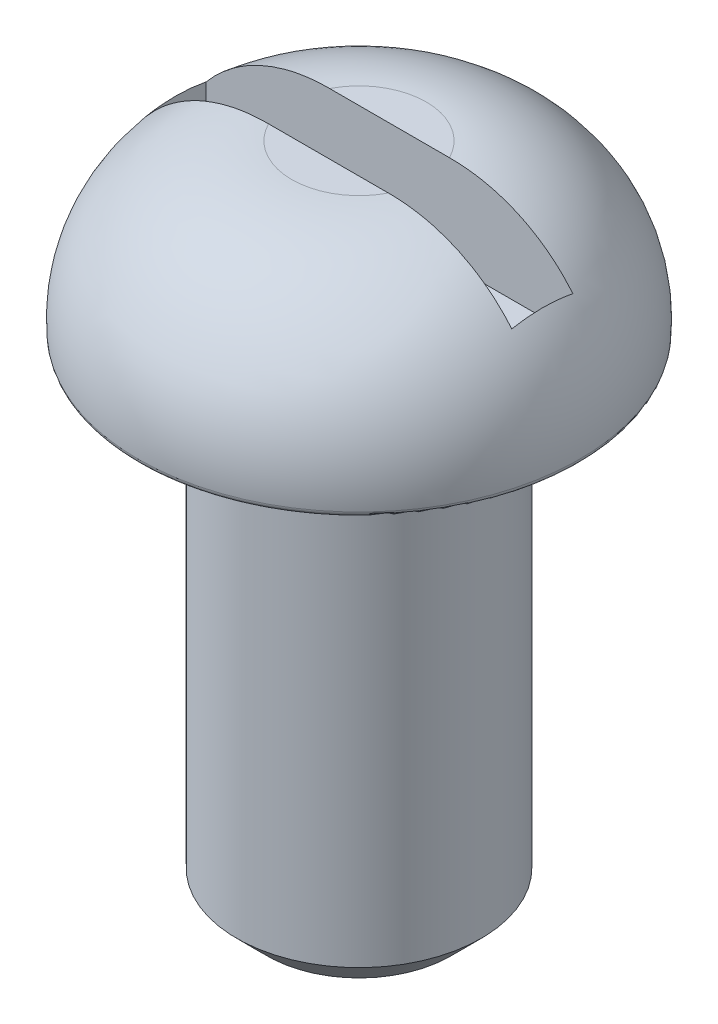
SolidWorks part; units mm, degrees
ref_plane "Спереди" through (0, 0, 0) normal (0, 0, 1) x (1, 0, 0)
ref_plane "Сверху" through (0, 0, 0) normal (0, 1, 0) x (1, 0, 0)
ref_plane "Справа" through (0, 0, 0) normal (1, 0, 0) x (0, 0, -1)
sketch "Эскиз1" plane through (0, 0, 0) normal (0, 0, 1) x (1, 0, 0)
  line L0 (3.6, 8) -> (2, 8)
  line L1 (0, 0) -> (0, 10.8)
  line L2 (2, 8) -> (2, 0.5)
  line L3 (2, 0.5) -> (1.5, 0)
  line L4 (1.5, 0) -> (0, 0)
  line L5 (0, 10.8) -> (1.1, 10.8)
  arc A0 (1.1, 10.8) -> (3.6, 8) centre (1.1, 8.2839) cw
  dimension "D2" = 1.1
  dimension "D1" = 8
  dimension "D3" = 2
  dimension "D4" = 1.5
  dimension "D5" = 2.8
  dimension "D6" = 3.6
  dimension "D7" = 45
revolve "Повернуть1" add sketch "Эскиз1" angle 360 about L1
fillet "Скругление1" radius 0.1 1 edges at (0, 8, -3.6)
sketch "Эскиз3" plane through (0, 10.8, 0) normal (0, 1, 0) x (-1, 0, 0)
  line L1 (3, -0.5) -> (-3, -0.5)
  line L2 (3, -0.5) -> (3, 0.5)
  line L3 (3, 0.5) -> (-3, 0.5)
  line L4 (-3, -0.5) -> (-3, 0.5)
  dimension "D1" = 1
  dimension "D2" = 0.5
  dimension "D3" = 6
  dimension "D4" = 3
extrude "Вырез-Вытянуть2" cut sketch "Эскиз3" against normal blind 1.5
ref_axis "Ось1" through (0, -104.1565, 0) along (0, 1, 0)
